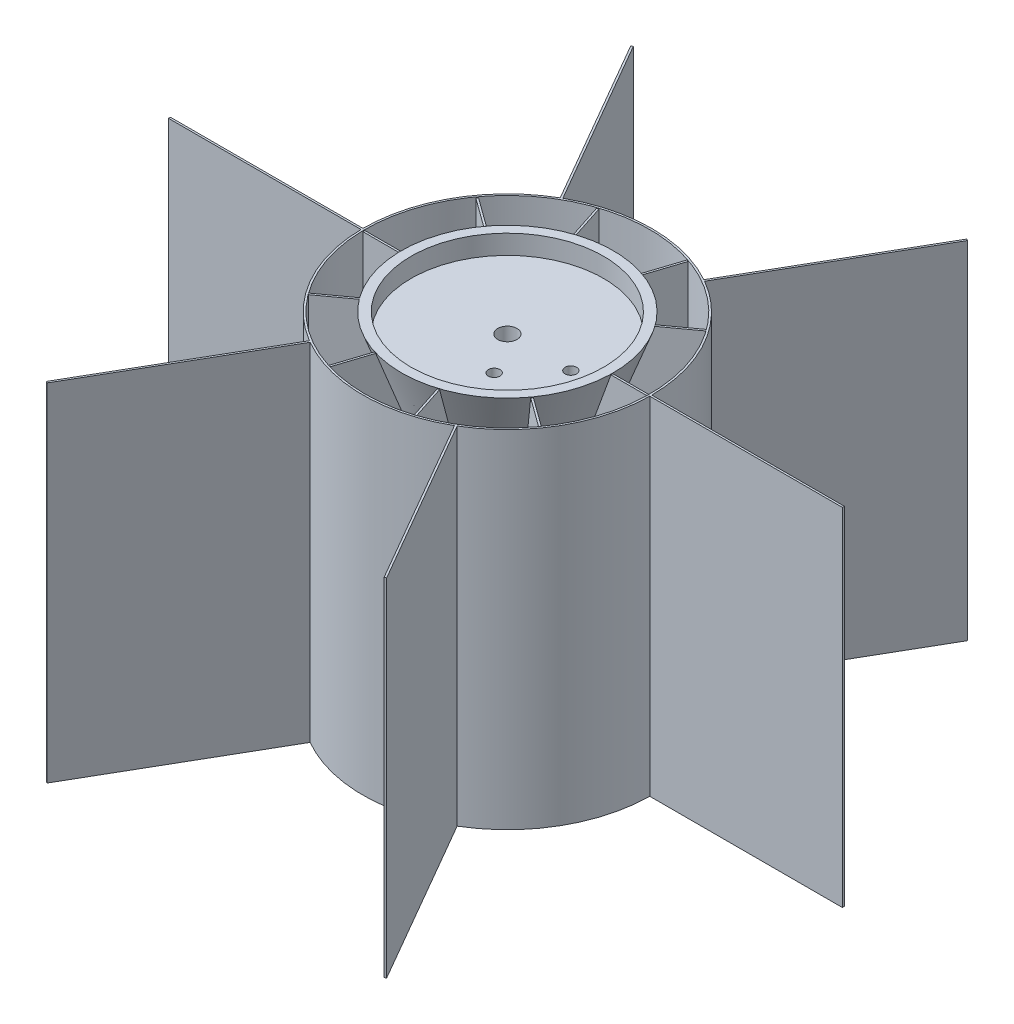
SolidWorks part; units mm, degrees
ref_plane "Front Plane" through (0, 0, 0) normal (0, 0, 1) x (1, 0, 0)
ref_plane "Top Plane" through (0, 0, 0) normal (0, 1, 0) x (1, 0, 0)
ref_plane "Right Plane" through (0, 0, 0) normal (1, 0, 0) x (0, 0, -1)
sketch "Sketch2" plane through (0, 0, 0) normal (0, 1, 0) x (1, 0, 0)
  circle A0 centre (0, 0) radius 75
  circle A1 centre (0, 0) radius 74
extrude "Boss-Extrude1" add sketch "Sketch2" along normal blind 180
ref_plane "Plane1" through (0, 180, 0) normal (0, 1, 0) x (1, 0, 0)
ref_plane "Plane2" through (0, 30, 0) normal (0, 1, 0) x (1, 0, 0)
sketch "Sketch3" plane through (0, 30, 0) normal (0, 1, 0) x (1, 0, 0)
  point P0 (0, 0)
sketch "Sketch4" plane through (0, 180, 0) normal (0, 1, 0) x (1, 0, 0)
  circle A0 centre (0, 0) radius 55
loft "Loft1" add profiles "Sketch4", "Sketch3"
ref_plane "Plane3" through (0, 105, 0) normal (0, 1, 0) x (1, 0, 0)
sketch "Sketch7" plane through (0, 105, 0) normal (0, 1, 0) x (1, 0, 0)
  line L0 (-74, 0) -> (-1.7013, 0)
  line L1 (-22.8673, 70.3782) -> (-0.5257, 1.618)
  line L2 (59.8673, 43.4961) -> (1.3764, 1)
  line L3 (59.8673, -43.4961) -> (1.3764, -1)
  line L4 (-22.8673, -70.3782) -> (-0.5257, -1.618)
  line L5 (-73.9932, -1) -> (-3.0777, -1)
  line L6 (-23.8162, 70.0627) -> (-1.9021, 2.618)
  line L7 (59.274, 44.3012) -> (1.9021, 2.618)
  line L8 (60.4496, -42.6831) -> (3.0777, -1)
  line L9 (-21.9141, -70.6808) -> (0, -3.2361)
  line L10 (-99.1947, -1) -> (106.1093, -1) construction
  line L11 (-99.1947, 0) -> (106.1093, 0) construction
  line L12 (0, -3.2361) -> (21.9141, -70.6808)
  line L15 (0.3249, -1) -> (1.3764, -1)
  line L16 (-1.3764, -1) -> (-59.8673, -43.4961)
  line L17 (-0.7265, -1) -> (-0.5257, -1.618)
  line L18 (-3.0777, -1) -> (-60.4496, -42.6831)
  line L19 (-1.3764, -1) -> (-0.7265, -1)
  line L21 (-1.1756, 0.382) -> (-1.7013, 0)
  line L22 (-1.3764, 1) -> (-59.8673, 43.4961)
  line L23 (-1.3764, 1) -> (-1.1756, 0.382)
  line L24 (-1.9021, 2.618) -> (-59.274, 44.3012)
  line L25 (0.3249, -1) -> (22.8673, -70.3782)
  line L26 (0.5257, 1.618) -> (0, 1.2361)
  line L27 (0, 1.2361) -> (-0.5257, 1.618)
  line L28 (0.5257, 1.618) -> (22.8673, 70.3782)
  line L29 (1.9021, 2.618) -> (23.8162, 70.0627)
  line L30 (1.1756, 0.382) -> (1.3764, 1)
  line L31 (1.7013, 0) -> (74, 0)
  line L32 (3.0777, -1) -> (73.9932, -1)
  line L33 (1.7013, 0) -> (1.1756, 0.382)
  circle A0 centre (0, 0) radius 27.5 construction
  arc A1 (-74, 0) -> (-73.9932, -1) centre (0, 0) ccw
  arc A2 (-60.4496, -42.6831) -> (-59.8673, -43.4961) centre (0, 0) ccw
  arc A3 (-59.274, 44.3012) -> (-59.8673, 43.4961) centre (0, 0) ccw
  arc A4 (-22.8673, 70.3782) -> (-23.8162, 70.0627) centre (0, 0) ccw
  arc A5 (23.8162, 70.0627) -> (22.8673, 70.3782) centre (0, 0) ccw
  arc A6 (59.8673, 43.4961) -> (59.274, 44.3012) centre (0, 0) ccw
  arc A7 (73.9932, -1) -> (74, 0) centre (0, 0) ccw
  arc A8 (59.8673, -43.4961) -> (60.4496, -42.6831) centre (0, 0) ccw
  arc A9 (21.9141, -70.6808) -> (22.8673, -70.3782) centre (0, 0) ccw
  arc A10 (-22.8673, -70.3782) -> (-21.9141, -70.6808) centre (0, 0) ccw
  point P18 (0, 0)
  point P29 (0, 0)
  dimension "D1" = 5
  dimension "D2" = 1
  dimension "D3" = 5
extrude "Boss-Extrude2" add sketch "Sketch7" along normal blind 74.5
sketch "Sketch8" plane through (0, 0, 0) normal (0, 1, 0) x (1, 0, 0)
  circle A0 centre (0, 0) radius 15
extrude "Boss-Extrude3" add sketch "Sketch8" along normal up to surface (70.9091 mm away) up to face at (13.297, 151.5625, 42.5421)
sketch "Sketch9" plane through (0, 0, 0) normal (1, 0, 0) x (0, 0, -1)
  circle A1 centre (0, 10) radius 3
extrude "Boss-Extrude4" add sketch "Sketch9" along normal up to surface (73.9392 mm away) up to face at (22.3909, 142.25, 70.5303)
sketch "Sketch10" plane through (0, 0, 0) normal (1, 0, 0) x (0, 0, -1)
  circle A1 centre (0, 10) radius 3
extrude "Boss-Extrude5" add sketch "Sketch10" against normal up to surface (73.9392 mm away) up to face at (0, 0, 74)
sketch "Sketch11" plane through (0, 0, 0) normal (0, 0, 1) x (1, 0, 0)
  circle A1 centre (0, 10) radius 3
extrude "Boss-Extrude6" add sketch "Sketch11" along normal up to surface (73.9392 mm away) up to face at (-73.9424, 9.3127, 2.9202)
sketch "Sketch12" plane through (0, 0, 0) normal (0, 0, 1) x (1, 0, 0)
  circle A1 centre (0, 10) radius 3
extrude "Boss-Extrude7" add sketch "Sketch12" against normal up to surface (73.9392 mm away) up to face at (73.9424, 9.3127, -2.9202)
fillet "Fillet1" radius 10 1 edges at (0, 70.9091, 15)
fillet "Fillet2" radius 2 4 edges at (0.6233, 7.0655, -14.987) (14.7102, 10.6236, -2.9345) (-14.7102, 9.3764, 2.9345) (2.9345, 10.6236, 14.7102)
fillet "Fillet3" radius 2 4 edges at (2.9202, 9.3127, 73.9424) (73.9424, 9.3127, -2.9202) (0.6873, 7.0798, -73.9968) (-73.9424, 9.3127, 2.9202)
sketch "Sketch19" plane through (0, 180, 0) normal (0, 1, 0) x (1, 0, 0)
  circle A0 centre (0, 0) radius 50
extrude "Cut-Extrude1" cut sketch "Sketch19" against normal blind 10
sketch "Sketch20" plane through (0, 180, 0) normal (0, 1, 0) x (1, 0, 0)
  circle A0 centre (0, 0) radius 5
extrude "Cut-Extrude2" cut sketch "Sketch20" against normal blind 20
sketch "Sketch21" plane through (0, 180, 0) normal (0, 1, 0) x (1, 0, 0)
  circle A0 centre (32.973, 0) radius 3
  circle A1 centre (14.0704, -20.9215) radius 3
extrude "Cut-Extrude3" cut sketch "Sketch21" against normal blind 20
sketch "Sketch22" plane through (0, 0, 0) normal (0, -1, 0) x (1, 0, 0)
  circle A0 centre (0, 0) radius 6
extrude "Cut-Extrude4" cut sketch "Sketch22" against normal blind 20
cosmetic thread "Cosmetic Thread1" parameters "D1"=20, "D2"=14
sketch "Sketch23" plane through (0, 0, 0) normal (0, 1, 0) x (1, 0, 0)
  line L0 (-175, 0) -> (-75, 0)
  line L1 (87.5, 151.5544) -> (37.5, 64.9519)
  line L2 (87.5, -151.5544) -> (37.5, -64.9519)
  line L3 (-174.9971, -1) -> (-74.9933, -1)
  line L4 (86.6325, 152.052) -> (36.6306, 65.4461)
  line L5 (88.3646, -151.052) -> (38.3627, -64.4461)
  line L6 (-329.3744, -1) -> (318.2765, -1) construction
  line L7 (-329.3744, 0) -> (318.2765, 0) construction
  line L8 (75, 0) -> (175, 0)
  line L9 (74.9933, -1) -> (174.9971, -1)
  line L12 (-37.5, -64.9519) -> (-87.5, -151.5544)
  line L13 (-38.3627, -64.4461) -> (-88.3646, -151.052)
  line L16 (-37.5, 64.9519) -> (-87.5, 151.5544)
  line L17 (-36.6306, 65.4461) -> (-86.6325, 152.052)
  arc A0 (-38.3627, -64.4461) -> (-37.5, -64.9519) centre (0, 0) ccw
  arc A1 (87.5, -151.5544) -> (88.3646, -151.052) centre (0, 0) ccw
  arc A2 (-88.3646, -151.052) -> (-87.5, -151.5544) centre (0, 0) ccw
  arc A3 (-175, 0) -> (-174.9971, -1) centre (0, 0) ccw
  arc A4 (-86.6325, 152.052) -> (-87.5, 151.5544) centre (0, 0) ccw
  arc A5 (87.5, 151.5544) -> (86.6325, 152.052) centre (0, 0) ccw
  arc A6 (174.9971, -1) -> (175, 0) centre (0, 0) ccw
  arc A7 (37.5, -64.9519) -> (38.3627, -64.4461) centre (0, 0) ccw
  arc A8 (74.9933, -1) -> (75, 0) centre (0, 0) ccw
  arc A9 (37.5, 64.9519) -> (36.6306, 65.4461) centre (0, 0) ccw
  arc A10 (-36.6306, 65.4461) -> (-37.5, 64.9519) centre (0, 0) ccw
  arc A11 (-75, 0) -> (-74.9933, -1) centre (0, 0) ccw
  point P10 (0, 0)
  point P20 (0, 0)
  dimension "D2" = 1
  dimension "D1" = 3
  dimension "D3" = 3
extrude "Boss-Extrude9" add sketch "Sketch23" along normal blind 180
